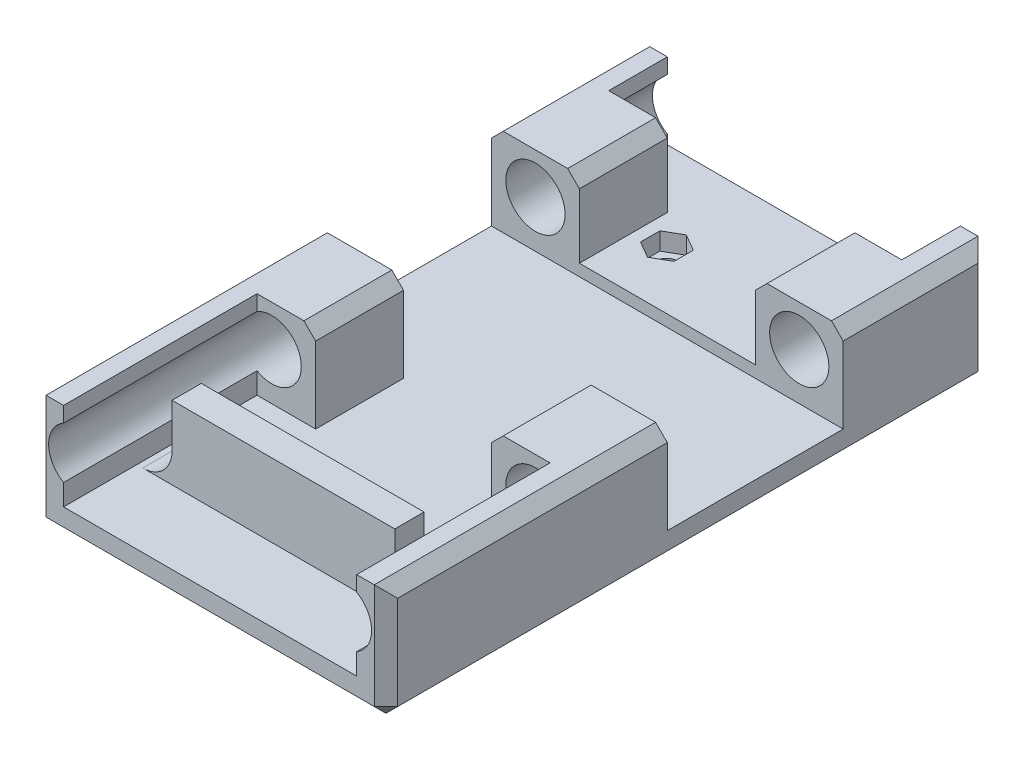
SolidWorks part; units mm, degrees
ref_plane "Front Plane" through (0, 0, 0) normal (0, 0, 1) x (1, 0, 0)
ref_plane "Top Plane" through (0, 0, 0) normal (0, 1, 0) x (1, 0, 0)
ref_plane "Right Plane" through (0, 0, 0) normal (1, 0, 0) x (0, 0, -1)
sketch "Sketch1" plane through (0, 0, 0) normal (0, 1, 0) x (1, 0, 0)
  line L1 (30, 30) -> (-30, 30)
  line L2 (30, 30) -> (30, -30)
  line L3 (30, -30) -> (-30, -30)
  line L4 (-30, 30) -> (-30, -30)
  line L5 (30, 30) -> (-30, -30) construction
  line L6 (30, -30) -> (-30, 30) construction
  point P0 (0, 0)
  dimension "D1" = 60
  dimension "D2" = 60
extrude "Boss-Extrude1" add sketch "Sketch1" along normal blind 5
sketch "Sketch2" plane through (0, 5, 0) normal (0, 1, 0) x (1, 0, 0)
  line L0 (-30, 30) -> (-30, -30) construction
  line L1 (-30, 30) -> (-15, 30)
  line L2 (-30, 30) -> (-30, 15)
  line L3 (-30, 15) -> (-15, 15)
  line L4 (-15, 30) -> (-15, 15)
  line L5 (30, -30) -> (30, 30) construction
  line L6 (30, 30) -> (15, 30)
  line L7 (30, 30) -> (30, 15)
  line L8 (30, 15) -> (15, 15)
  line L9 (15, 30) -> (15, 15)
  line L10 (30, 30) -> (-30, 30) construction
  line L11 (-30, -15) -> (-15, -15)
  line L12 (-30, -15) -> (-30, -30)
  line L13 (-30, -30) -> (-15, -30)
  line L14 (-15, -15) -> (-15, -30)
  line L15 (30, -15) -> (15, -15)
  line L16 (30, -15) -> (30, -30)
  line L17 (30, -30) -> (15, -30)
  line L18 (15, -15) -> (15, -30)
  line L19 (-30, -30) -> (30, -30) construction
  dimension "D1" = 15
  dimension "D2" = 15
extrude "Boss-Extrude2" add sketch "Sketch2" along normal blind 15
sketch "Sketch3" plane through (0, 0, 30) normal (0, 0, 1) x (1, 0, 0)
  line L0 (-30, 13) -> (30, 13) construction
  line L2 (30, 20) -> (30, 0) construction
  line L3 (-30, 20) -> (-30, 0) construction
  line L4 (-15, 5) -> (15, 5) construction
  line L5 (-22.5, 20) -> (-22.5, 0) construction
  line L6 (-30, 20) -> (-15, 20) construction
  line L7 (-30, 0) -> (30, 0) construction
  line L8 (22.5, 20) -> (22.5, 0) construction
  line L9 (15, 20) -> (30, 20) construction
  circle A0 centre (-22.5, 13) radius 5.05
  circle A1 centre (22.5, 13) radius 5.05
  point P3 (0, 13)
  point P19 (-22.5, 13)
  point P20 (22.5, 13)
  dimension "D2" = 10.1
  dimension "D3" = 10.1
  dimension "D1" = 8
extrude "Cut-Extrude1" cut sketch "Sketch3" against normal through all both and the other way through all
sketch "Sketch4" plane through (0, 0, 30) normal (0, 0, 1) x (1, 0, 0)
  line L0 (30, 20) -> (30, 0) construction
  line L1 (-30, 0) -> (30, 0)
  line L2 (-30, 0) -> (-30, 5)
  line L3 (-30, 5) -> (30, 5)
  line L4 (30, 0) -> (30, 5)
  line L5 (-15, 5) -> (15, 5) construction
extrude "Boss-Extrude3" add sketch "Sketch4" along normal blind 33
sketch "Sketch5" plane through (0, 0, -30) normal (0, 0, -1) x (-1, 0, 0)
  line L1 (-30, 0) -> (30, 0)
  line L2 (-30, 0) -> (-30, 5)
  line L3 (-30, 5) -> (30, 5)
  line L4 (30, 0) -> (30, 5)
extrude "Boss-Extrude4" add sketch "Sketch5" along normal blind 10
sketch "Sketch6" plane through (0, 5, 0) normal (0, 1, 0) x (1, 0, 0)
  line L0 (30, 40) -> (30, 30) construction
  line L5 (15, 30) -> (30, 30) construction
  line L6 (15, 30) -> (15, 15) construction
  line L8 (-15, 15) -> (-15, 30) construction
  line L9 (-30, 30) -> (-15, 30) construction
  line L10 (-30, 40) -> (-30, 30) construction
  line L11 (-30, 40) -> (30, 40) construction
  line L12 (30, 40) -> (30, 30)
  line L13 (15, 30) -> (30, 30)
  line L14 (15, 30) -> (15, 15)
  line L15 (-15, 15) -> (-15, 30)
  line L16 (-30, 30) -> (-15, 30)
  line L17 (-30, 40) -> (-30, 30)
  line L18 (-30, 40) -> (30, 40)
  line L19 (-15, 15) -> (15, 15)
extrude "Boss-Extrude5" add sketch "Sketch6" along normal blind 2
sketch "Sketch8" plane through (0, 7, 0) normal (0, 1, 0) x (1, 0, 0)
  line L0 (0, 40) -> (0, -63) construction
  line L1 (30, 40) -> (-30, 40) construction
  line L2 (30, -63) -> (-30, -63) construction
  line L3 (-10.07, 25) -> (10.07, 25) construction
  line L5 (-7.2121, 23.35) -> (-7.2121, 26.65)
  line L6 (-7.2121, 26.65) -> (-10.07, 28.3)
  line L7 (-10.07, 28.3) -> (-12.9279, 26.65)
  line L8 (-12.9279, 26.65) -> (-12.9279, 23.35)
  line L9 (-12.9279, 23.35) -> (-10.07, 21.7)
  line L10 (-10.07, 21.7) -> (-7.2121, 23.35)
  line L11 (12.9279, 23.35) -> (12.9279, 26.65)
  line L12 (12.9279, 26.65) -> (10.07, 28.3)
  line L13 (10.07, 28.3) -> (7.2121, 26.65)
  line L14 (7.2121, 26.65) -> (7.2121, 23.35)
  line L15 (7.2121, 23.35) -> (10.07, 21.7)
  line L16 (10.07, 21.7) -> (12.9279, 23.35)
  circle A0 centre (-10.07, 25) radius 2.8579 construction
  circle A1 centre (10.07, 25) radius 2.8579 construction
  point P9 (0, 25)
  point P24 (10.07, 25)
  point P25 (-10.07, 25)
  dimension "D1" = 20.14
  dimension "D2" = 15
  dimension "D3" = 3.3
extrude "Cut-Extrude2" cut sketch "Sketch8" against normal blind 3
hole_wizard "M3 Clearance Hole1" positions "Sketch10" profile "Sketch11" hole size "M3" standard "ANSI Metric" end condition through all
sketch "Sketch10" plane through (0, 7, 0) normal (0, 1, 0) x (1, 0, 0)
  point P0 (-10.07, 25)
  point P3 (10.07, 25)
sketch "Sketch11" plane through (-10.07, 7, -25) normal (1, 0, 0) x (0, 0, 1)
  line L0 (0, 0) -> (0, 7)
  line L1 (0, 7) -> (1.7, 7)
  line L2 (1.7, 7) -> (1.7, 0.025)
  line L3 (1.7, 0.025) -> (1.725, 0)
  line L5 (1.725, 0) -> (0, 0)
  line L6 (-1.7, 0.025) -> (-1.725, 0) construction
  line L11 (0, -6.35) -> (0, 107.95) construction
  dimension "Thru Hole Dia." = 3.4
  dimension "Thru Hole Depth" = 7
  dimension "Near C'Sink Dia." = 3.45
  dimension "Near C'Sink Angle" = 90
sketch "Sketch13" plane through (0, 5, 0) normal (0, 1, 0) x (1, 0, 0)
  line L10 (30, -63) -> (-30, -63) construction
  line L11 (30, -30) -> (25, -30)
  line L12 (30, -30) -> (30, -63)
  line L13 (30, -63) -> (25, -63)
  line L14 (25, -30) -> (25, -63)
  line L15 (-15, 30) -> (-30, 30) construction
  line L16 (-30, -30) -> (-25, -30)
  line L17 (-30, -30) -> (-30, -63)
  line L18 (-30, -63) -> (-25, -63)
  line L19 (-25, -30) -> (-25, -63)
  line L20 (-30, 40) -> (-25, 40)
  line L21 (-30, 40) -> (-30, 30)
  line L22 (-30, 30) -> (-25, 30)
  line L23 (-25, 40) -> (-25, 30)
  line L24 (30, 30) -> (15, 30) construction
  line L25 (30, 40) -> (25, 40)
  line L26 (30, 40) -> (30, 30)
  line L27 (30, 30) -> (25, 30)
  line L28 (25, 40) -> (25, 30)
  dimension "D1" = 5
extrude "Boss-Extrude6" add sketch "Sketch13" along normal up to surface (15 mm away) up to face at (-22.5, 20, -22.5)
chamfer "Chamfer1" distance 2 angle 45 16 edges at (0, 0, -40) (30, 10, 63) (30, 10, -40) (30, 0, 11.5) (0, 0, 63) (-30, 10, 63) (-30, 0, 11.5) (-30, 10, -40) (30, 20, 39) (15, 20, 22.5) (-30, 20, 39) (-15, 20, 22.5) (30, 20, -27.5) (15, 20, -22.5) (-15, 20, -22.5) (-30, 20, -27.5)
sketch "Sketch14" plane through (0, 0, 30) normal (0, 0, 1) x (1, 0, 0)
  circle A0 centre (-22.5, 13) radius 5.05
  circle A1 centre (22.5, 13) radius 5.05
  arc A2 (-25, 8.6122) -> (-25, 17.3878) centre (-22.5, 13) ccw construction
extrude "Cut-Extrude3" cut sketch "Sketch14" against normal mid plane 200
sketch "Sketch15" plane through (0, 5, 0) normal (0, 1, 0) x (1, 0, 0)
  line L1 (-19, -50.5) -> (19, -50.5)
  line L2 (-19, -50.5) -> (-19, -45.5)
  line L3 (-19, -45.5) -> (19, -45.5)
  line L4 (19, -50.5) -> (19, -45.5)
  line L6 (25, -63) -> (-25, -63) construction
  line L7 (0, -45.5) -> (0, -63) construction
  line L8 (0, -63) -> (0, 42.3099) construction
  point P11 (0, 0)
  dimension "D1" = 5
  dimension "D2" = 12.5
  dimension "D3" = 38
extrude "Boss-Extrude7" add sketch "Sketch15" along normal blind 12.5
fillet "Fillet1" radius 5 2 edges at (-19, 5, 48) (19, 5, 48)
